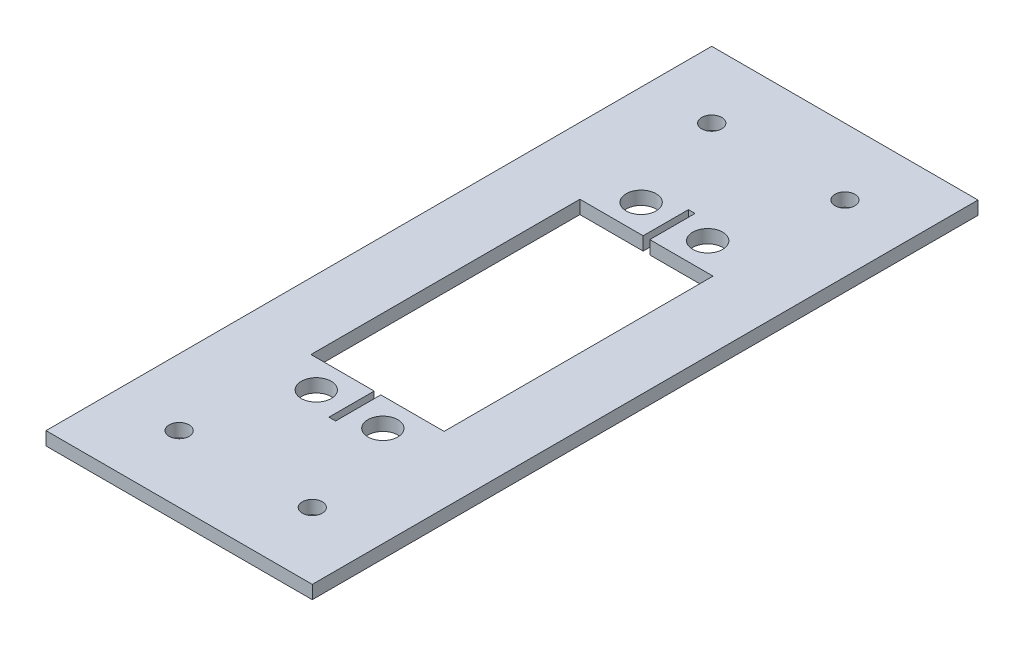
SolidWorks part; units mm, degrees
ref_plane "Front Plane" through (0, 0, 0) normal (0, 0, 1) x (1, 0, 0)
ref_plane "Top Plane" through (0, 0, 0) normal (0, 1, 0) x (1, 0, 0)
ref_plane "Right Plane" through (0, 0, 0) normal (1, 0, 0) x (0, 0, -1)
sketch "Sketch1" plane through (0, 0, 0) normal (0, 1, 0) x (1, 0, 0)
  line L0 (0.736, 26.632) -> (1.236, 26.632)
  line L1 (0.736, 26.632) -> (0.736, 19.832)
  line L2 (0.736, 19.832) -> (1.236, 19.832)
  line L3 (1.236, 26.632) -> (1.236, 19.832)
  line L4 (0.736, 26.632) -> (0.236, 26.632)
  line L5 (0.736, 26.632) -> (0.736, 19.832)
  line L6 (0.736, 19.832) -> (0.236, 19.832)
  line L7 (0.236, 26.632) -> (0.236, 19.832)
  line L8 (0.736, 19.832) -> (10.736, 19.832)
  line L9 (0.736, 19.832) -> (0.736, -20.568)
  line L10 (0.736, -20.568) -> (10.736, -20.568)
  line L11 (10.736, 19.832) -> (10.736, -20.568)
  line L12 (0.736, 19.832) -> (-9.264, 19.832)
  line L13 (0.736, 19.832) -> (0.736, -20.568)
  line L14 (0.736, -20.568) -> (-9.264, -20.568)
  line L15 (-9.264, 19.832) -> (-9.264, -20.568)
  line L16 (0.736, -20.568) -> (1.236, -20.568)
  line L17 (0.736, -20.568) -> (0.736, -27.368)
  line L18 (0.736, -27.368) -> (1.236, -27.368)
  line L19 (1.236, -20.568) -> (1.236, -27.368)
  line L20 (0.736, -20.568) -> (0.236, -20.568)
  line L21 (0.736, -20.568) -> (0.736, -27.368)
  line L22 (0.736, -27.368) -> (0.236, -27.368)
  line L23 (0.236, -20.568) -> (0.236, -27.368)
  line L25 (-19.264, 49.632) -> (20.736, 49.632)
  line L26 (-19.264, 49.632) -> (-19.264, -50.368)
  line L27 (-19.264, -50.368) -> (20.736, -50.368)
  line L28 (20.736, 49.632) -> (20.736, -50.368)
  circle A0 centre (-4.264, 24.032) radius 2.25
  circle A1 centre (5.736, 24.032) radius 2.25
  circle A2 centre (5.736, -24.768) radius 2.25
  circle A3 centre (-4.264, -24.768) radius 2.25
  circle A4 centre (-9.264, 39.632) radius 1.5
  circle A5 centre (10.736, 39.632) radius 1.5
  circle A6 centre (10.736, -40.368) radius 1.5
  circle A7 centre (-9.264, -40.368) radius 1.5
  dimension "D24" = 10
  dimension "D26" = 10
  dimension "D27" = 10
  dimension "D28" = 10
  dimension "D29" = 10
  dimension "D30" = 10
  dimension "D31" = 10
  dimension "D1" = 0.5
  dimension "D2" = 0.5
  dimension "D3" = 6.8
  dimension "D4" = 40.4
  dimension "D5" = 10
  dimension "D6" = 10
  dimension "D7" = 4.5
  dimension "D8" = 4.2
  dimension "D9" = 4.5
  dimension "D10" = 4.2
  dimension "D11" = 0.5
  dimension "D12" = 0.5
  dimension "D13" = 6.8
  dimension "D14" = 4.2
  dimension "D15" = 4.5
  dimension "D16" = 4.5
  dimension "D17" = 4.2
  dimension "D18" = 100
  dimension "D19" = 40
  dimension "D20" = 23
  dimension "D21" = 23
  dimension "D22" = 10
  dimension "D23" = 10
  dimension "D25" = 10
extrude "Boss-Extrude1" add sketch "Sketch1" along normal blind 2 contours L28 L25 L26 L27 A7 A6 A5 A4 A3 A2 A1 A0 L23 L14 L15 L12 L7 L4 L0 L3 L8 L11 L10 L19 L18 L22 region at (0.736, 0, -48.555)
